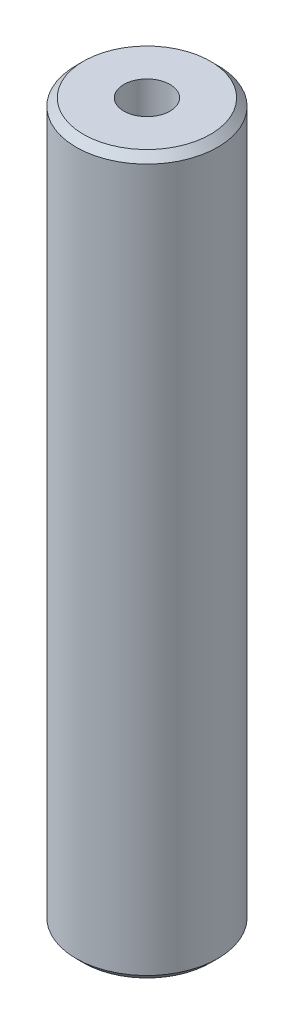
SolidWorks part; units mm, degrees
ref_plane "Front Plane" through (0, 0, 0) normal (0, 0, 1) x (1, 0, 0)
ref_plane "Top Plane" through (0, 0, 0) normal (0, 1, 0) x (1, 0, 0)
ref_plane "Right Plane" through (0, 0, 0) normal (1, 0, 0) x (0, 0, -1)
sketch "Sketch1" plane through (0, 0, 0) normal (0, 1, 0) x (1, 0, 0)
  circle A0 centre (0, 0) radius 42.5
  dimension "SHAFT_OD" = 85
extrude "Boss-Extrude1" add sketch "Sketch1" along normal blind 430.4875
sketch "Sketch2" plane through (0, 0, 0) normal (0, 1, 0) x (1, 0, 0)
  circle A0 centre (0, 0) radius 13.8711
  dimension "BORE_D" = 27.7423
extrude "Cut-Extrude1" cut sketch "Sketch2" along normal through all
chamfer "Chamfer1" distance 4.4384 angle 45 2 edges at (0, 430.4875, 42.5) (0, 0, 42.5)
